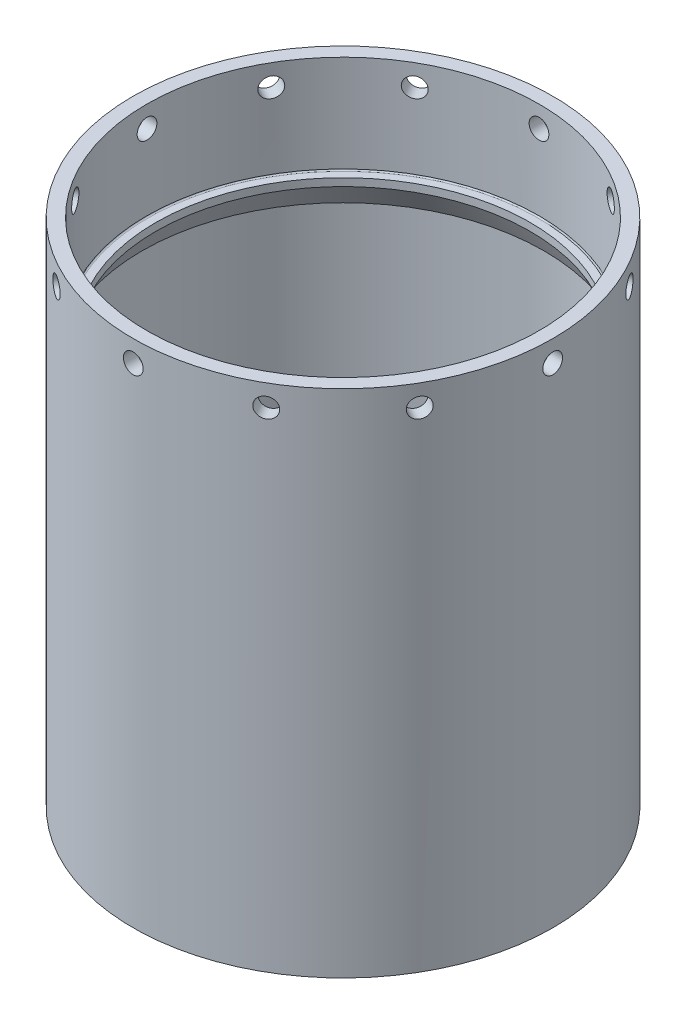
SolidWorks part; units mm, degrees
material "AISI 304"
ref_plane "Front Plane" through (0, 0, 0) normal (0, 0, 1) x (1, 0, 0)
ref_plane "Top Plane" through (0, 0, 0) normal (0, 1, 0) x (1, 0, 0)
ref_plane "Right Plane" through (0, 0, 0) normal (1, 0, 0) x (0, 0, -1)
sketch "Sketch2" plane through (0, 0, 0) normal (0, 0, 1) x (1, 0, 0)
  line L4 (0, 0) -> (0, -101.6) construction
  line L6 (61.849, 0) -> (64.8208, 0)
  line L7 (61.849, 0) -> (61.849, -2.54)
  line L8 (57.15, -136.1974) -> (69.342, -136.1974)
  line L9 (69.342, 32.385) -> (69.342, -136.1974)
  line L12 (64.8208, 0) -> (64.8208, 32.385)
  line L13 (64.8208, 32.385) -> (69.342, 32.385)
  line L14 (61.849, -2.54) -> (66.3575, -10.349)
  line L15 (66.3575, -10.349) -> (66.3575, -111.949)
  line L17 (59.69, -131.798) -> (59.69, -123.4974)
  line L18 (59.69, -123.4974) -> (66.3575, -111.949)
  line L19 (59.69, -131.798) -> (57.15, -136.1974)
  dimension "D5" = 32.385
  dimension "D7" = 129.6416
  dimension "D2" = 123.698
  dimension "D3" = 4.5212
  dimension "D4" = 132.715
  dimension "D8" = 138.684
  dimension "D9" = 30
  dimension "D10" = 2.54
  dimension "D11" = 30
  dimension "D14" = 119.38
  dimension "D15" = 114.3
  dimension "D16" = 30
  dimension "D12" = 12.7
  dimension "D6" = 101.6
  dimension "D13" = 168.5824
revolve "Revolve1" add sketch "Sketch2" angle 360 about L4
fillet "Fillet1" radius 0.4064 1 edges at (-64.8208, 0, 0)
ref_plane "Plane1" through (0, 0, 69.342) normal (0, 0, 1) x (1, 0, 0)
sketch "Sketch3" plane through (0, 0, 69.342) normal (0, 0, 1) x (1, 0, 0)
  line L1 (64.4144, 0) -> (-64.4144, 0) construction
  point P0 (0, 25.3111)
  dimension "D1" = 25.3111
hole_wizard "F (0.257) Injector Hole" positions "Sketch3" profile "Sketch4" hole size "F" standard "ANSI Inch" end condition up to next
sketch "Sketch4" plane through (0, 25.3111, 69.342) normal (1, 0, 0) x (0, -1, 0)
  line L0 (0, 0) -> (0, 4.5212)
  line L1 (0, 4.5212) -> (3.2639, 4.5212)
  line L2 (3.2639, 4.5212) -> (3.2639, 0)
  line L5 (3.2639, 0) -> (0, 0)
  line L11 (0, -6.35) -> (0, 107.95) construction
  dimension "Thru Hole Dia." = 6.5278
  dimension "Thru Hole Depth" = 4.5212
sketch "Sketch5" plane through (0, -136.1974, 0) normal (0, -1, 0) x (1, 0, 0)
  line L0 (0, 64.516) -> (-61.3584, 19.9365) construction
  line L1 (-61.3584, 19.9365) -> (-37.9216, -52.1945) construction
  line L2 (-37.9216, -52.1945) -> (37.9216, -52.1945) construction
  line L3 (37.9216, -52.1945) -> (61.3584, 19.9365) construction
  line L4 (61.3584, 19.9365) -> (0, 64.516) construction
  circle A1 centre (0, 0) radius 64.516 construction
  point P0 (0, 64.516)
  point P8 (61.3584, 19.9365)
  point P10 (37.9216, -52.1945)
  point P12 (-37.9216, -52.1945)
  point P14 (-61.3584, 19.9365)
  dimension "D1" = 129.032
hole_wizard "1/4-20 Tapped Nozzle Hole" positions "Sketch5" profile "Sketch6" tap size "1/4-20" standard "ANSI Inch"
sketch "Sketch6" plane through (0, -136.1974, 64.516) normal (1, 0, 0) x (0, 0, -1)
  line L0 (0, 0) -> (0, 14.2338)
  line L1 (0, 14.2338) -> (2.5527, 12.7)
  line L2 (2.5527, 12.7) -> (2.5527, 6.985)
  line L3 (2.5527, 6.985) -> (3.175, 6.985)
  line L4 (3.175, 6.985) -> (3.175, 0)
  line L5 (3.175, 0) -> (0, 0)
  line L10 (0, 14.2338) -> (-2.5527, 12.7) construction
  line L11 (0, -6.35) -> (0, 107.95) construction
  dimension "Tap Drill Dia." = 5.1054
  dimension "Tap Drill Depth" = 12.7
  dimension "Thread Major Dia." = 6.35
  dimension "Thread Depth" = 6.985
  dimension "Drill Angle" = 118
pattern_circular "CirPattern1" count 12 over 360 about axis through (0, 0, 0) along (0, 1, 0) of "F (0.257) Injector Hole" reverse direction yes
equation "\"length\"= 4in"
equation "\"bearingThickness\"= 0.178in"
equation "\"chamberID\"=5.225"
equation "\"D3@Sketch2\"=\"bearingThickness\""
equation "\"D4@Sketch2\"=\"chamberID\""
equation "\"D6@Sketch2\"=\"length\""
equation "\"D1@Sketch3\"=0.990in+0.0065"
